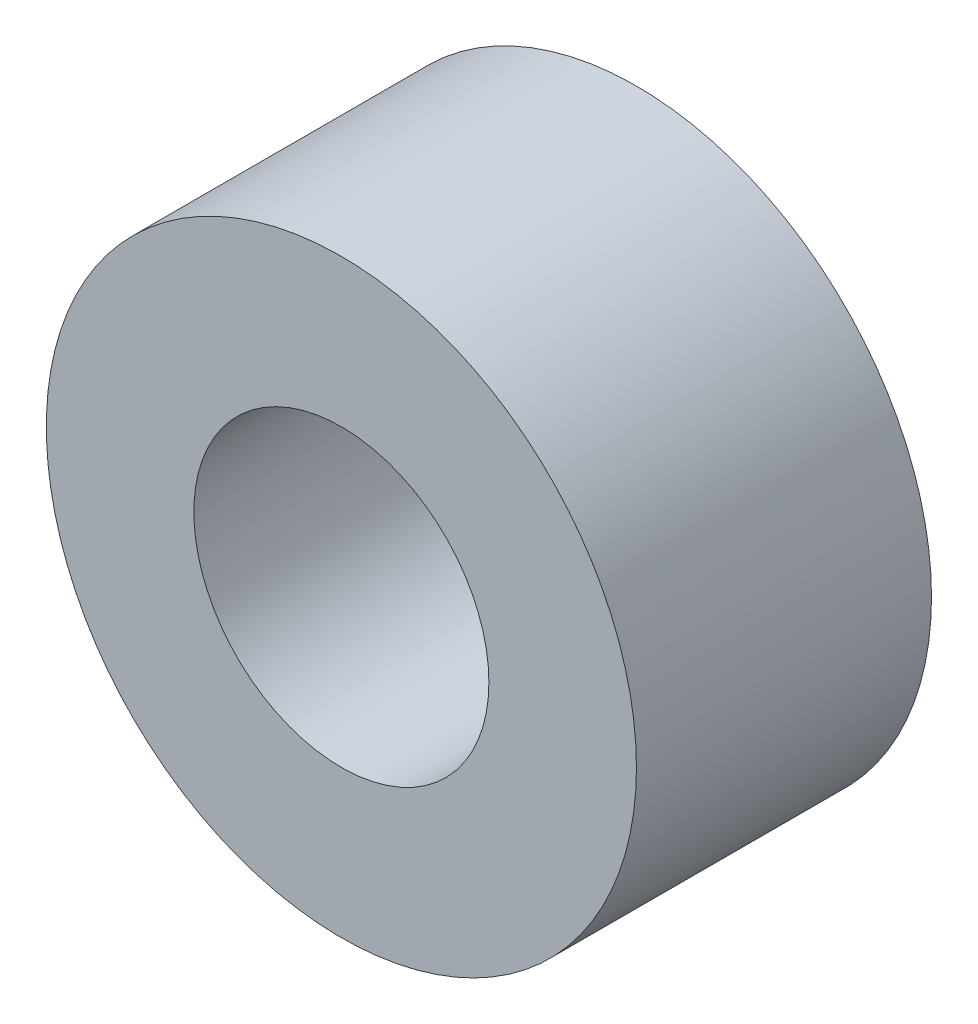
SolidWorks part; units mm, degrees
ref_plane "前视基准面" through (0, 0, 0) normal (0, 0, 1) x (1, 0, 0)
ref_plane "上视基准面" through (0, 0, 0) normal (0, 1, 0) x (1, 0, 0)
ref_plane "右视基准面" through (0, 0, 0) normal (1, 0, 0) x (0, 0, -1)
sketch "草图1" plane through (0, 0, 0) normal (0, 0, 1) x (1, 0, 0)
  circle A0 centre (0, 0) radius 1
  circle A1 centre (0, 0) radius 2
extrude "凸台-拉伸2" add sketch "草图1" along normal blind 2
